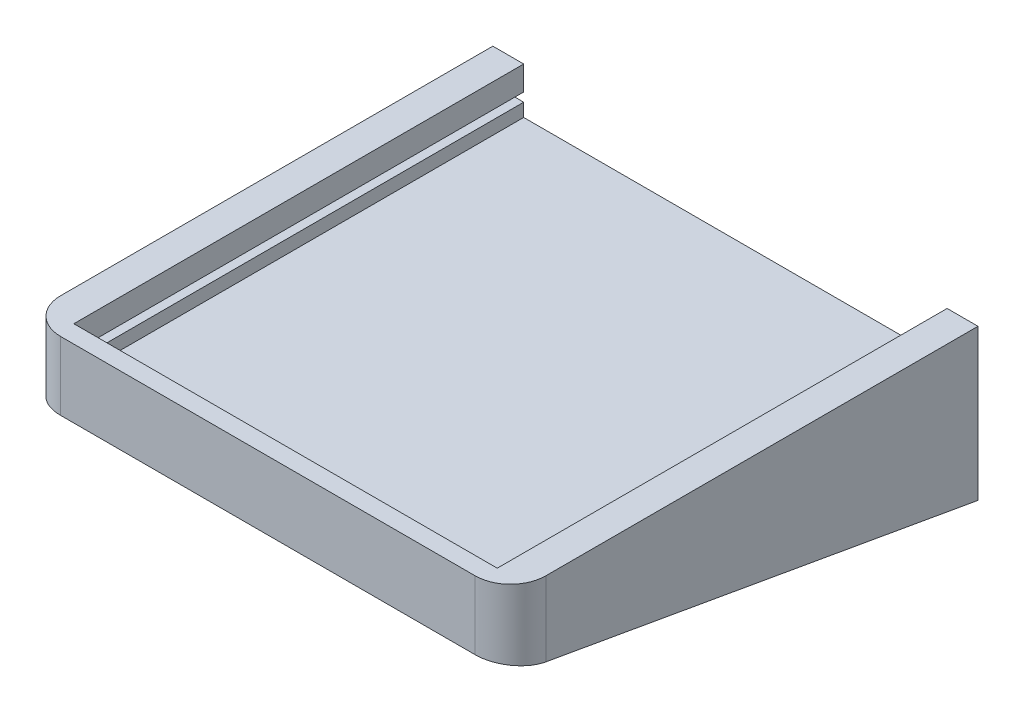
SolidWorks part; units mm, degrees
ref_plane "Plan de face" through (0, 0, 0) normal (0, 0, 1) x (1, 0, 0)
ref_plane "Plan de dessus" through (0, 0, 0) normal (0, 1, 0) x (1, 0, 0)
ref_plane "Plan de droite" through (0, 0, 0) normal (1, 0, 0) x (0, 0, -1)
sketch "Esquisse2" plane through (0, 0, 0) normal (0, 1, 0) x (1, 0, 0)
  line L1 (0, 0) -> (110, 0)
  line L2 (0, 0) -> (0, 106)
  line L3 (0, 106) -> (110, 106)
  line L4 (110, 0) -> (110, 106)
  dimension "D1" = 110
  dimension "D2" = 106
extrude "Boss.-Extru.3" add sketch "Esquisse2" along normal blind 5
sketch "Esquisse3" plane through (0, 5, 0) normal (0, 1, 0) x (1, 0, 0)
  line L0 (7, 106) -> (7, 4)
  line L1 (0, 106) -> (110, 106)
  line L2 (0, 106) -> (0, 0)
  line L3 (0, 0) -> (110, 0)
  line L4 (110, 106) -> (110, 0)
  line L5 (7, 4) -> (103, 4)
  line L6 (103, 4) -> (103, 106)
  line M8 (0, 106) -> (0, 0)
  line M9 (0, 0) -> (110, 0)
  line M10 (110, 0) -> (110, 106)
  line M11 (110, 106) -> (0, 106)
  dimension "D1" = 7
  dimension "D2" = 7
  dimension "D3" = 4
extrude "Boss.-Extru.4" add sketch "Esquisse3" along normal blind 3 contours L6 L5 L0 M11 M8 M9 M10 region at (5.4724, 5, -55)
sketch "Esquisse4" plane through (0, 8, 0) normal (0, 1, 0) x (1, 0, 0)
  line L0 (4, 106) -> (4, 4)
  line L7 (106, 106) -> (106, 4)
  line L15 (4, 106) -> (0, 106)
  line L16 (0, 106) -> (0, 0)
  line L17 (0, 0) -> (110, 0)
  line L18 (110, 0) -> (110, 106)
  line L19 (110, 106) -> (106, 106)
  line L21 (4, 4) -> (106, 4)
  dimension "D1" = 4
  dimension "D2" = 4
  dimension "D3" = 4
extrude "Boss.-Extru.5" add sketch "Esquisse4" along normal blind 2 contours L0 L21 L7 L19 L18 L17 L16 L15
sketch "Esquisse6" plane through (0, 10, 0) normal (0, 1, 0) x (1, 0, 0)
  line L0 (103, 4) -> (103, 106) construction
  line L1 (0, 106) -> (7, 106)
  line L2 (0, 106) -> (0, 4)
  line L4 (7, 106) -> (7, 4)
  line L6 (103, 4) -> (103, 106)
  line L7 (103, 106) -> (110, 106)
  line L8 (110, 4) -> (110, 106)
  line L9 (103, 4) -> (103, 106) construction
  line L11 (110, 0) -> (0, 0)
  line L12 (110, 0) -> (110, 4)
  line L13 (103, 4) -> (7, 4)
  line L14 (0, 0) -> (0, 4)
extrude "Boss.-Extru.6" add sketch "Esquisse6" along normal blind 5.5
sketch "Esquisse8" plane through (110, 0, 0) normal (1, 0, 0) x (0, 0, -1)
  line L0 (0, 0) -> (106, 0)
  line L1 (0, 0) -> (106, 0) construction
  line L2 (106, 0) -> (106, -18.6907)
  line L3 (106, -18.6907) -> (0, 0)
  line L5 (106, 15.5) -> (106, 0) construction
  dimension "D1" = 10
extrude "Boss.-Extru.7" add sketch "Esquisse8" against normal blind 110
sketch "Esquisse7" plane through (0, 0, -106) normal (0, 0, -1) x (-1, 0, 0)
  line L0 (-103, 8) -> (-103, 5) construction
  line L1 (-103, 8) -> (-106, 8) construction
  line L2 (-7, 8) -> (-7, 5) construction
  line L3 (-7, 8) -> (-4, 8) construction
  circle A0 centre (-103, 0) radius 2.35
  circle A1 centre (-7, 0) radius 2.35
  dimension "D1" = 4.7
  dimension "D2" = 4.7
  dimension "D3" = 0
  dimension "D4" = 8
  dimension "D5" = 0
  dimension "D6" = 8
extrude "Enlèv. mat.-Extru.1" cut sketch "Esquisse7" against normal blind 4
fillet "Congé3" radius 8 2 edges at (110, 7.75, 0) (0, 7.75, 0)
sketch "Esquisse9" plane through (0, 0, 0) normal (0, -0.9848, 0.1736) x (1, 0, 0)
  line L0 (0, -8.1234) -> (0, -107.6352) construction
  line L1 (14, -8) -> (96, -8)
  line L2 (8, -14) -> (8, -97.6352)
  line L3 (14, -103.6352) -> (96, -103.6352)
  line L4 (102, -14) -> (102, -97.6352)
  line L5 (110, -8.1234) -> (110, -107.6352) construction
  line L6 (8, 0) -> (102, 0) construction
  line L7 (0, -107.6352) -> (110, -107.6352) construction
  arc A0 (8, -97.6352) -> (14, -103.6352) centre (14, -97.6352) ccw
  arc A1 (96, -103.6352) -> (102, -97.6352) centre (96, -97.6352) ccw
  arc A2 (96, -8) -> (102, -14) centre (96, -14) cw
  arc A3 (14, -8) -> (8, -14) centre (14, -14) ccw
  dimension "D5" = 6
  dimension "D1" = 8
  dimension "D2" = 8
  dimension "D3" = 8
  dimension "D4" = 4
extrude "Enlèv. mat.-Extru.2" cut sketch "Esquisse9" against normal blind 4 contours L2 A0 L3 A1 L4 A2 L1 A3
